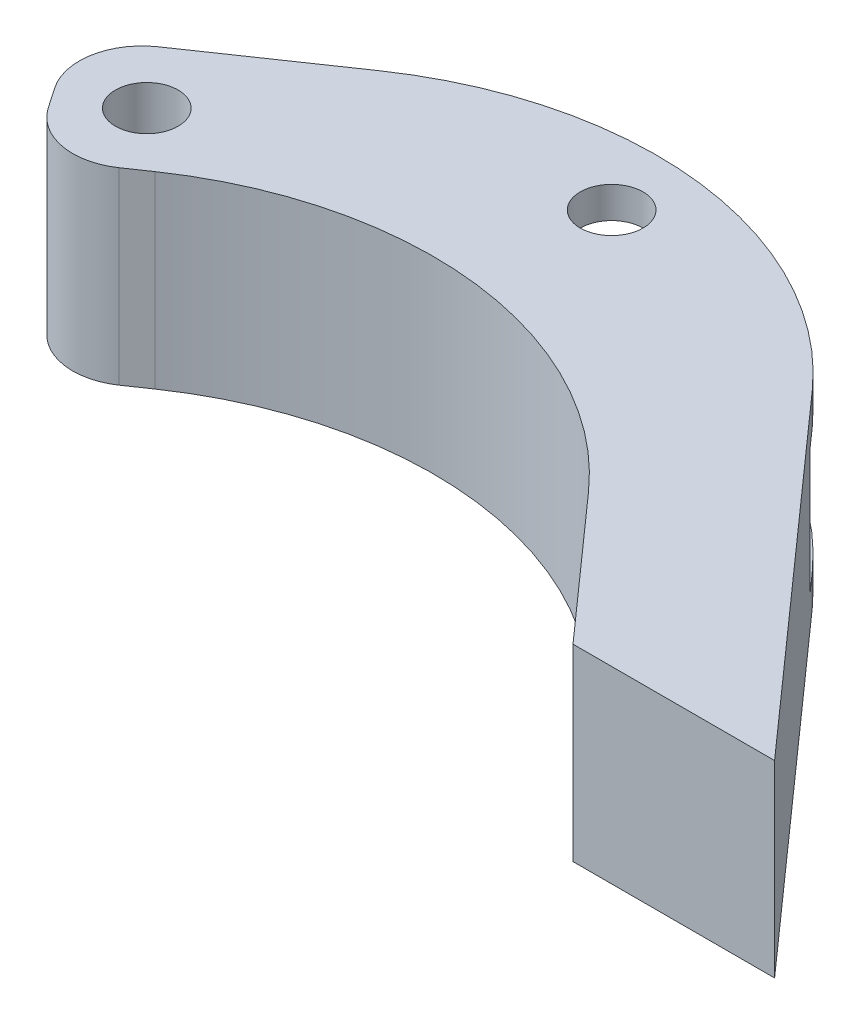
SolidWorks part; units mm, degrees
ref_plane "Front Plane" through (0, 0, 0) normal (0, 0, 1) x (1, 0, 0)
ref_plane "Top Plane" through (0, 0, 0) normal (0, 1, 0) x (1, 0, 0)
ref_plane "Right Plane" through (0, 0, 0) normal (1, 0, 0) x (0, 0, -1)
sketch "Sketch3" plane through (0, 0, 0) normal (0, 1, 0) x (1, 0, 0)
  point P0 (0, 0)
  line B0 (0, 0) -> (16.0555, 0)
  line B1 (-7.9359, 26.9902) -> (16.0555, 0)
  line B2 (-9.8821, 11.1174) -> (0, 0)
  line B3 (-47.3009, 31.817) -> (-61.8386, 21.8682)
  line B4 (-61.8386, 21.8682) -> (-55.0615, 11.9652)
  line B5 (-49.2472, 15.9442) -> (-55.0615, 11.9652)
  circle B6 centre (-53.9445, 20) radius 2.5
  arc B7 (-7.9359, 26.9902) -> (-47.3009, 31.817) centre (-30.3581, 7.0593) ccw
  arc B8 (-9.8821, 11.1174) -> (-49.2472, 15.9442) centre (-32.3044, -8.8135) ccw
  circle B9 centre (-28.4081, 31.4871) radius 2.5
sketch_block_instance "Block1-1"
sketch_block "Block1"
extrude "Boss-Extrude2" add sketch "Sketch3" along normal mid plane 15
sketch "Sketch6" plane through (0, 0, 0) normal (0, 1, 0) x (1, 0, 0)
  line L2 (-47.3009, 31.817) -> (-61.8386, 21.8682) construction
  line L3 (-47.3009, 31.817) -> (-61.8386, 21.8682)
  circle A2 centre (-28.4081, 31.4871) radius 2.5 construction
  circle A3 centre (-28.4081, 31.4871) radius 2.5 construction
  arc A5 (-7.9359, 26.9902) -> (-47.3009, 31.817) centre (-30.3581, 7.0593) ccw construction
  arc A6 (-7.9359, 26.9902) -> (-47.3009, 31.817) centre (-30.3581, 7.0593) ccw
  spline S0 degree 3 poles (-14.7922, 32.705) (-17.3319, 26.216) (-31.2969, 23.2593) (-41.248, 30.9651) (-47.3009, 31.817) knots 0 0 0 0 0.502708 1 1 1 1
  point P2 (-39.3469, 30.3714)
  point P6 (-48.7829, 30.8028)
  point P9 (-47.3009, 31.817)
  point P10 (-39.5787, 28.6829)
  point P12 (-35.2085, 26.7296)
  point P15 (-20.774, 26.6303)
  point P16 (-40.605, 28.2856)
  point P17 (-47.3009, 31.817)
  point P18 (-47.3009, 31.817)
  point P19 (-39.7408, 29.4258)
  point P21 (-30.3581, 25.9379)
extrude "Cut-Extrude2" cut sketch "Sketch6" against normal mid plane 10 contours S0 A6 region at (-29.4655, 0, -31.603)
fillet "Fillet1" radius 10 2 edges at (-14.7922, 0, -32.705) (-47.3009, 0, -31.817)
fillet "Fillet2" radius 5 2 edges at (-55.0615, 0, -11.9652) (-61.8386, 0, -21.8682)
